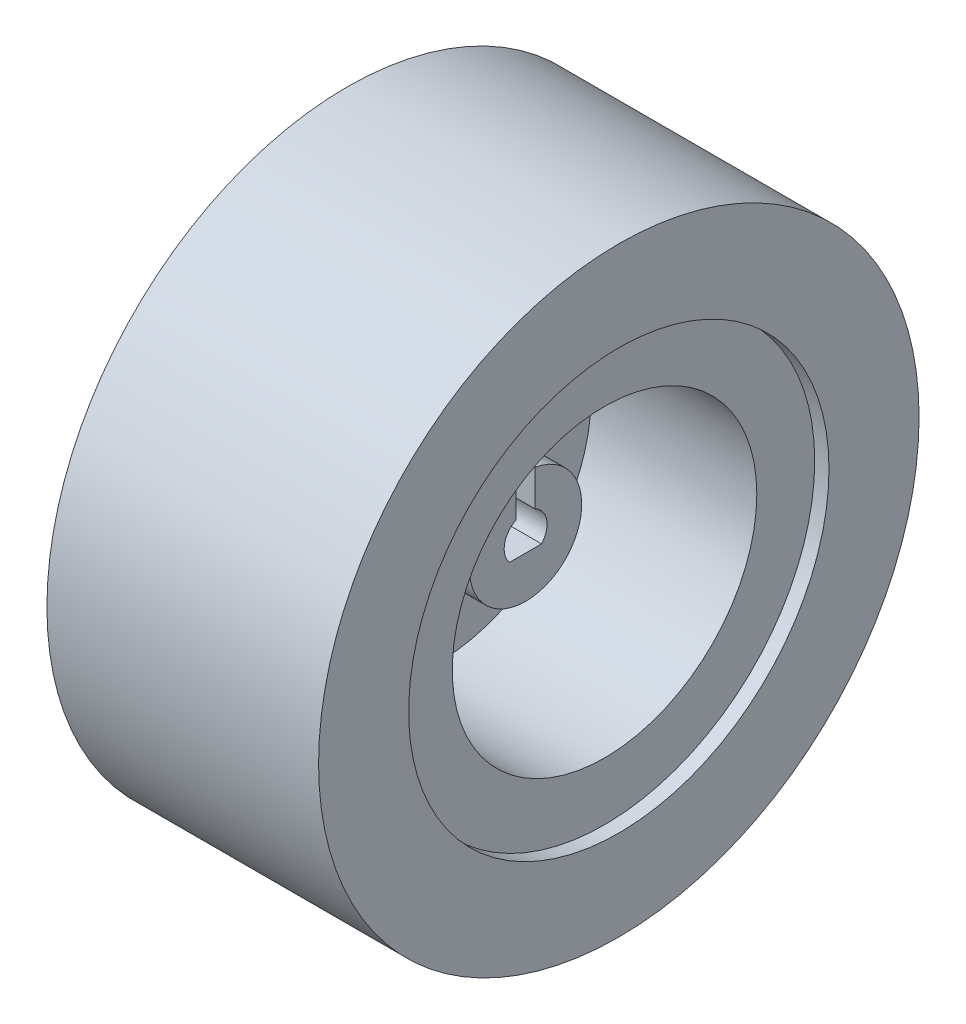
SolidWorks part; units mm, degrees
ref_plane "Front Plane" through (0, 0, 0) normal (0, 0, 1) x (1, 0, 0)
ref_plane "Top Plane" through (0, 0, 0) normal (0, 1, 0) x (1, 0, 0)
ref_plane "Right Plane" through (0, 0, 0) normal (1, 0, 0) x (0, 0, -1)
sketch "Sketch1" plane through (0, 0, 0) normal (1, 0, 0) x (0, 0, -1)
  circle A0 centre (0, 0) radius 21
  dimension "D1" = 42
extrude "Boss-Extrude1" add sketch "Sketch1" along normal blind 9.5 and the other way blind 9.5
sketch "Sketch5" plane through (9.5, 0, 0) normal (1, 0, 0) x (0, 0, -1)
  circle A0 centre (0, 0) radius 14.7
  dimension "D1" = 29.4
extrude "Cut-Extrude3" cut sketch "Sketch5" against normal blind 1
sketch "Sketch6" plane through (8.5, 0, 0) normal (1, 0, 0) x (0, 0, -1)
  circle A0 centre (0, 0) radius 10.65
  dimension "D1" = 21.3
extrude "Cut-Extrude4" cut sketch "Sketch6" against normal blind 11.6
sketch "Sketch7" plane through (-3.1, 0, 0) normal (1, 0, 0) x (0, 0, -1)
  circle A0 centre (0, 0) radius 3.925
  dimension "D1" = 7.85
extrude "Boss-Extrude2" add sketch "Sketch7" along normal blind 6.08
sketch "Sketch2" plane through (9.5, 0, 0) normal (1, 0, 0) x (0, 0, -1)
  line L0 (-1.9974, 0) -> (-0.665, 0) construction
  line L1 (-1.118, -1) -> (1.118, -1)
  line L2 (-0.665, 8.8797) -> (-0.665, 1.3445)
  line L3 (-0.665, 8.8797) -> (0.665, 8.8797)
  line L5 (0.665, 8.8797) -> (0.665, 1.3445)
  line L6 (-0.665, 8.8797) -> (0.4507, 1.4307) construction
  line L7 (-0.4507, 1.4307) -> (0.665, 8.8797) construction
  line L8 (0.665, 0) -> (2.227, 0) construction
  arc A0 (1.118, -1) -> (0.665, 1.3445) centre (0, 0) ccw
  arc A1 (-0.665, 1.3445) -> (-1.118, -1) centre (0, 0) ccw
  point P5 (0, 4.4399)
  dimension "D1" = 3
  dimension "D2" = 1
  dimension "D3" = 8.8797
  dimension "D4" = 1.33
extrude "Cut-Extrude1" cut sketch "Sketch2" against normal through all
sketch "Sketch4" plane through (-9.5, 0, 0) normal (-1, 0, 0) x (0, 0, 1)
  circle A0 centre (0, 0) radius 14.7
  dimension "D1" = 29.4
extrude "Cut-Extrude2" cut sketch "Sketch4" against normal blind 4.5
equation "\"wheel diam\"= 42mm"
equation "\"wheel_hole\"= 3.0"
equation "\"wheel_depth\"= 19mm"
equation "\"D1@Sketch1\"= \"wheel diam\""
equation "\"D1@Sketch2\"= \"wheel_hole\""
